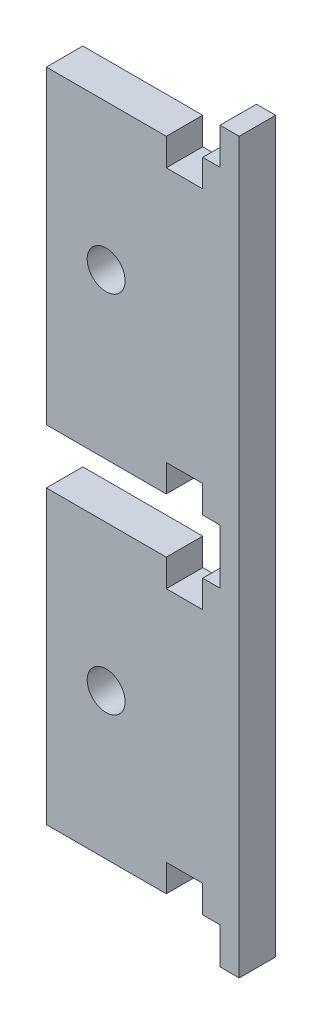
SolidWorks part; units mm, degrees
material "AISI 4130 Steel, annealed at 865C"
ref_plane "X-Y Datum" through (0, 0, 0) normal (0, 0, 1) x (1, 0, 0)
ref_plane "X-Z Datum" through (0, 0, 0) normal (0, 1, 0) x (1, 0, 0)
ref_plane "Y-Z Datum" through (0, 0, 0) normal (1, 0, 0) x (0, 0, -1)
sketch "Sketch2" plane through (0, 0, 0) normal (0, 0, 1) x (1, 0, 0)
  line L0 (34.925, 127) -> (0, 127) construction
  line L1 (0, 0) -> (40.64, 0)
  line L2 (0, 0) -> (0, 127)
  line L3 (0, 127) -> (40.64, 127)
  line L4 (40.64, 0) -> (40.64, 127)
  point P7 (17.4625, 31.75)
  point P8 (17.4625, 95.25)
  dimension "D1" = 40.64
extrude "Boss-Extrude1" add sketch "Sketch2" along normal blind 6.35
hole_wizard "M6 Clearance Hole1" positions "Sketch3" profile "Sketch4" hole size "M6" standard "ANSI Metric" end condition through all
sketch "Sketch3" plane through (0, 0, 6.35) normal (0, 0, 1) x (1, 0, 0)
  point P0 (17.4625, 31.75)
  point P3 (17.4625, 95.25)
sketch "Sketch4" plane through (17.4625, 31.75, 6.35) normal (1, 0, 0) x (0, -1, 0)
  line L0 (0, 0) -> (0, 6.35)
  line L1 (0, 6.35) -> (3.3, 6.35)
  line L2 (3.3, 6.35) -> (3.3, 0)
  line L5 (3.3, 0) -> (0, 0)
  line L11 (0, -6.35) -> (0, 107.95) construction
  dimension "Thru Hole Dia." = 6.6
  dimension "Thru Hole Depth" = 6.35
sketch "Sketch5" plane through (0, 0, 6.35) normal (0, 0, 1) x (1, 0, 0)
  line L0 (7.0505, 127) -> (7.0505, 0)
  line L1 (40.64, 127) -> (0, 127) construction
  line L2 (0, 0) -> (40.64, 0) construction
  circle A0 centre (17.4625, 95.25) radius 3.3 construction
  point P6 (14.1625, 95.25)
  line M4 (0, 127) -> (0, 0)
  line M5 (0, 0) -> (40.64, 0)
  line M7 (40.64, 127) -> (0, 127)
  dimension "D1" = 7.112
extrude "Cut-Extrude1" cut sketch "Sketch5" against normal through all and the other way through all contours L0 M7 M4 M5 region at (3.5252, 63.5, 6.35)
sketch "Sketch6" plane through (0, 0, 6.35) normal (0, 0, 1) x (1, 0, 0)
  line L0 (-3.175, 120.65) -> (38.1, 120.65)
  line L1 (38.1, 120.65) -> (38.1, 130.175)
  line L2 (38.1, 130.175) -> (-3.175, 130.175)
  line L3 (-3.175, 130.175) -> (-3.175, 120.65)
  line L4 (0, 123.825) -> (34.925, 123.825)
  line L5 (34.925, 123.825) -> (34.925, 127)
  line L6 (34.925, 127) -> (0, 127)
  line L7 (0, 127) -> (0, 123.825)
  line L8 (0, 123.825) -> (34.925, 123.825)
  line L9 (34.925, 123.825) -> (34.925, 127)
  line L10 (34.925, 127) -> (0, 127)
  line L11 (0, 127) -> (0, 123.825)
  line L12 (0, 60.325) -> (34.925, 60.325)
  line L13 (34.925, 60.325) -> (34.925, 63.5)
  line L14 (34.925, 63.5) -> (0, 63.5)
  line L15 (0, 63.5) -> (0, 60.325)
  line L16 (0, 60.325) -> (34.925, 60.325)
  line L17 (34.925, 60.325) -> (34.925, 63.5)
  line L18 (34.925, 63.5) -> (0, 63.5)
  line L19 (0, 63.5) -> (0, 60.325)
  line L24 (0, 0) -> (34.925, 0)
  line L25 (34.925, 0) -> (34.925, 3.175)
  line L26 (34.925, 3.175) -> (0, 3.175)
  line L27 (0, 3.175) -> (0, 0)
  line L28 (38.1, 66.675) -> (-3.175, 66.675)
  line L29 (-3.175, 66.675) -> (-3.175, 57.15)
  line L30 (-3.175, 57.15) -> (38.1, 57.15)
  line L31 (38.1, 57.15) -> (38.1, 66.675)
  line L32 (38.1, 6.35) -> (-3.175, 6.35)
  line L33 (-3.175, 6.35) -> (-3.175, -3.175)
  line L34 (-3.175, -3.175) -> (38.1, -3.175)
  line L35 (38.1, -3.175) -> (38.1, 6.35)
  line L36 (37.3062, 127) -> (37.3062, 0)
  line L37 (40.64, 127) -> (7.0505, 127) construction
  line L38 (7.0505, 0) -> (40.64, 0) construction
  line M19 (7.0505, 127) -> (7.0505, 0)
  line M20 (7.0505, 0) -> (40.64, 0)
  line M22 (40.64, 127) -> (7.0505, 127)
  dimension "D5" = 2.3813
  dimension "D1" = 0
  dimension "D2" = 0
  dimension "D4" = 3.175
extrude "Cut-Extrude2" cut sketch "Sketch6" against normal through all contours L36 L9 L8 L0 M22 M19 | L8 L9 M22 M19 | L36 L28 L18 L17 L16 L30 M19 | L17 L18 L16 M19 | L36 L32 L26 L25 M19 M20 | L25 L26 M19 M20 region at (23.1953, 122.4692, 6.35) region at (20.9877, 125.4125, 6.35) region at (22.1784, 66.3578, 6.35) region at (20.9877, 61.9125, 6.35) region at (23.1953, 4.5308, 6.35) region at (20.9878, 1.5875, 6.35)
sketch "Sketch7" plane through (0, 0, 6.35) normal (0, 0, 1) x (1, 0, 0)
  line L18 (34.29, 120.65) -> (27.94, 120.65)
  line L19 (34.29, 120.65) -> (34.29, 115.8875)
  line L20 (34.29, 115.8875) -> (27.94, 115.8875)
  line L21 (27.94, 120.65) -> (27.94, 115.8875)
  line L22 (34.29, 71.4375) -> (27.94, 71.4375)
  line L23 (34.29, 71.4375) -> (34.29, 66.675)
  line L24 (34.29, 66.675) -> (27.94, 66.675)
  line L25 (27.94, 71.4375) -> (27.94, 66.675)
  line L26 (34.29, 57.15) -> (27.94, 57.15)
  line L27 (34.29, 57.15) -> (34.29, 52.3875)
  line L28 (34.29, 52.3875) -> (27.94, 52.3875)
  line L29 (27.94, 57.15) -> (27.94, 52.3875)
  line L30 (34.29, 11.1125) -> (27.94, 11.1125)
  line L31 (34.29, 11.1125) -> (34.29, 6.35)
  line L32 (34.29, 6.35) -> (27.94, 6.35)
  line L33 (27.94, 11.1125) -> (27.94, 6.35)
extrude "Cut-Extrude3" cut sketch "Sketch7" against normal through all
